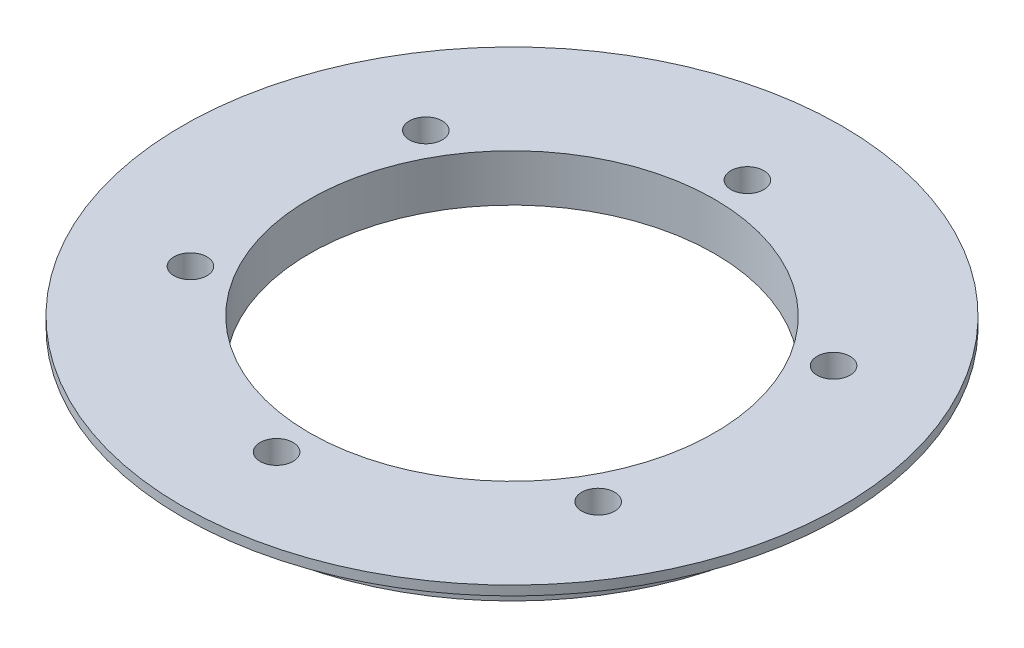
SolidWorks part; units mm, degrees
ref_plane "Front Plane" through (0, 0, 0) normal (0, 0, 1) x (1, 0, 0)
ref_plane "Top Plane" through (0, 0, 0) normal (0, 1, 0) x (1, 0, 0)
ref_plane "Right Plane" through (0, 0, 0) normal (1, 0, 0) x (0, 0, -1)
sketch "Sketch1" plane through (0, 0, 0) normal (0, 1, 0) x (1, 0, 0)
  circle A0 centre (0, 0) radius 30
  circle A2 centre (0, 0) radius 25 construction
  dimension "D1" = 60
  dimension "D2" = 50
extrude "Boss-Extrude1" add sketch "Sketch1" along normal blind 5
sketch "Sketch2" plane through (0, 5, 0) normal (0, 1, 0) x (1, 0, 0)
  circle A0 centre (0, 0) radius 35
  dimension "D1" = 70
extrude "Boss-Extrude2" add sketch "Sketch2" against normal blind 1
sketch "Sketch3" plane through (0, 0, 0) normal (0, -1, 0) x (1, 0, 0)
  circle A0 centre (0, 0) radius 21.5
  dimension "D1" = 43
extrude "Cut-Extrude1" cut sketch "Sketch3" against normal blind 25
sketch "Sketch4" plane through (0, 5, 0) normal (0, 1, 0) x (1, 0, 0)
  circle A0 centre (0, 0) radius 25 construction
  circle A1 centre (0, 25) radius 1.75
  circle A2 centre (0, 0) radius 25 construction
  circle A3 centre (21.6506, 12.5) radius 1.75
  circle A4 centre (0, 0) radius 25 construction
  circle A5 centre (21.6506, -12.5) radius 1.75
  circle A6 centre (0, 0) radius 25 construction
  circle A7 centre (0, -25) radius 1.75
  circle A8 centre (0, 0) radius 25 construction
  circle A9 centre (-21.6506, -12.5) radius 1.75
  circle A10 centre (0, 0) radius 25 construction
  circle A11 centre (-21.6506, 12.5) radius 1.75
  point P22 (0, 0)
  dimension "D1" = 50
  dimension "D2" = 3.5
  dimension "D3" = 6
extrude "Cut-Extrude2" cut sketch "Sketch4" against normal blind 25
